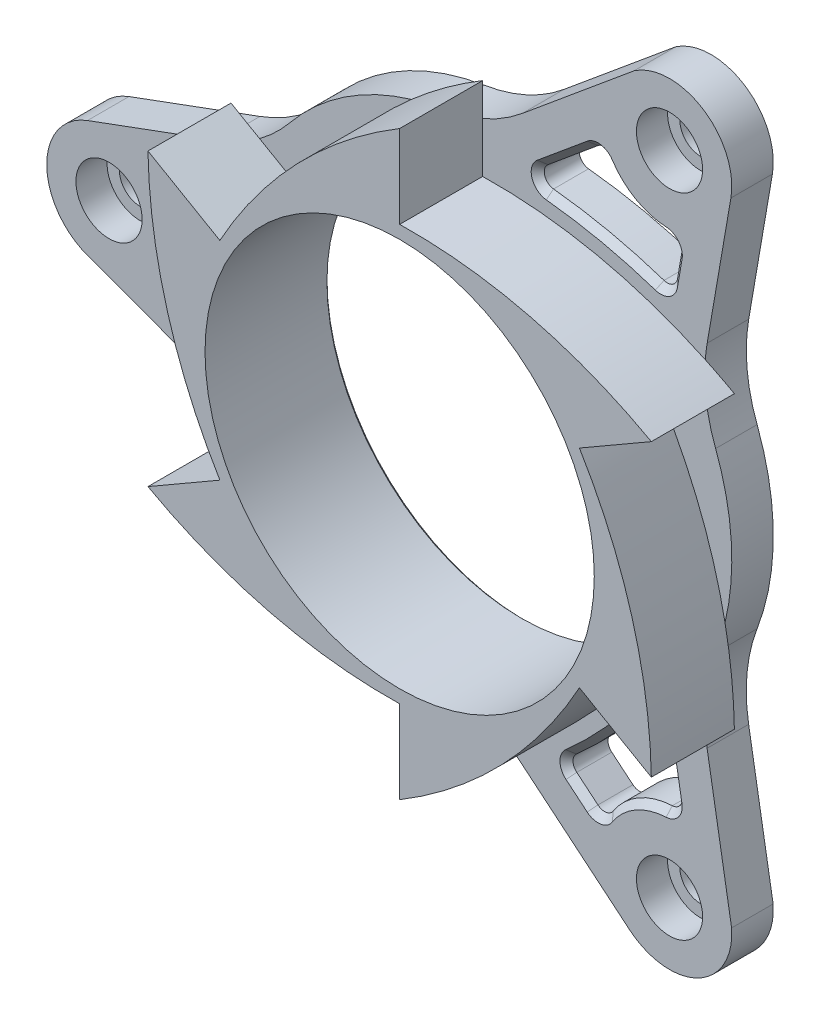
SolidWorks part; units mm, degrees
ref_plane "Front Plane" through (0, 0, 0) normal (0, 0, 1) x (1, 0, 0)
ref_plane "Top Plane" through (0, 0, 0) normal (0, 1, 0) x (1, 0, 0)
ref_plane "Right Plane" through (0, 0, 0) normal (1, 0, 0) x (0, 0, -1)
sketch "Sketch1" plane through (0, 0, 0) normal (0, 0, 1) x (1, 0, 0)
  line L0 (0, 0) -> (0, 31.75) construction
  line L1 (27.4963, 15.875) -> (38.4948, 22.225)
  line L2 (27.4963, -15.875) -> (38.4948, -22.225)
  line L3 (0, -31.75) -> (0, -44.45)
  line L4 (-27.4963, -15.875) -> (-38.4948, -22.225)
  line L5 (-27.4963, 15.875) -> (-38.4948, 22.225)
  line L6 (0, 31.75) -> (0, 44.45)
  line L7 (-20.9623, -0.7492) -> (-20.9623, -0.7492)
  line L8 (-9.8323, -18.5285) -> (-9.8323, -18.5285)
  line L9 (11.13, -17.7793) -> (11.13, -17.7793)
  line L10 (20.9623, 0.7492) -> (20.9623, 0.7492)
  line L11 (9.8323, 18.5285) -> (9.8323, 18.5285)
  line L12 (-11.13, 17.7793) -> (-11.13, 17.7793)
  line L13 (27.4963, 15.875) -> (24.4114, 20.9701) construction
  arc A0 (-11.13, 17.7793) -> (-20.9623, -0.7492) centre (39.2347, -20.8203) ccw
  arc A1 (38.4948, -22.225) -> (27.4963, 15.875) centre (-37.6483, -23.5681) ccw
  arc A2 (38.4948, 22.225) -> (0, 31.75) centre (1.5864, -44.3884) ccw
  arc A3 (0, -44.45) -> (27.4963, -15.875) centre (-39.2347, 20.8203) ccw
  arc A4 (-38.4948, -22.225) -> (0, -31.75) centre (-1.5864, 44.3884) ccw
  arc A5 (-38.4948, 22.225) -> (-27.4963, -15.875) centre (37.6483, 23.5681) ccw
  arc A6 (0, 44.45) -> (-27.4963, 15.875) centre (39.2347, -20.8203) ccw
  arc A7 (-20.9623, -0.7492) -> (-9.8323, -18.5285) centre (37.6483, 23.5681) ccw
  arc A8 (-9.8323, -18.5285) -> (11.13, -17.7793) centre (-1.5864, 44.3884) ccw
  arc A9 (11.13, -17.7793) -> (20.9623, 0.7492) centre (-39.2347, 20.8203) ccw
  arc A10 (20.9623, 0.7492) -> (9.8323, 18.5285) centre (-37.6483, -23.5681) ccw
  arc A11 (9.8323, 18.5285) -> (-11.13, 17.7793) centre (1.5864, -44.3884) ccw
  point P3 (0, 0)
  point P7 (42.5077, 12.9959)
  point P32 (0, 0)
  dimension "D1" = 6
  dimension "D2" = 12.7
  dimension "D3" = 60
extrude "Boss-Extrude1" add sketch "Sketch1" along normal blind 6.35 and the other way blind 6.35
sketch "Sketch3" plane through (0, 0, 6.35) normal (0, 0, 1) x (1, 0, 0)
  arc A0 (-11.13, 17.7793) -> (-20.9623, -0.7492) centre (39.2347, -20.8203) ccw construction
  arc A1 (9.8323, 18.5285) -> (-11.13, 17.7793) centre (1.5864, -44.3884) ccw construction
  arc A2 (20.9623, 0.7492) -> (9.8323, 18.5285) centre (-37.6483, -23.5681) ccw construction
  arc A3 (11.13, -17.7793) -> (20.9623, 0.7492) centre (-39.2347, 20.8203) ccw construction
  arc A4 (-9.8323, -18.5285) -> (11.13, -17.7793) centre (-1.5864, 44.3884) ccw construction
  arc A5 (-20.9623, -0.7492) -> (-9.8323, -18.5285) centre (37.6483, 23.5681) ccw construction
  arc A6 (-11.13, 17.7793) -> (-20.9623, -0.7492) centre (39.2347, -20.8203) ccw
  arc A7 (9.8323, 18.5285) -> (-11.13, 17.7793) centre (1.5864, -44.3884) ccw
  arc A8 (20.9623, 0.7492) -> (9.8323, 18.5285) centre (-37.6483, -23.5681) ccw
  arc A9 (11.13, -17.7793) -> (20.9623, 0.7492) centre (-39.2347, 20.8203) ccw
  arc A10 (-9.8323, -18.5285) -> (11.13, -17.7793) centre (-1.5864, 44.3884) ccw
  arc A11 (-20.9623, -0.7492) -> (-9.8323, -18.5285) centre (37.6483, 23.5681) ccw
extrude "Boss-Extrude2" add sketch "Sketch3" against normal blind 12.7
sketch "Sketch5" plane through (0, 0, -6.35) normal (0, 0, -1) x (-1, 0, 0)
  line L0 (0, 0) -> (57.15, 0) construction
  line L1 (0, 0) -> (0, 28.575) construction
  line L2 (32.9956, 19.05) -> (60.4429, 8.9377)
  line L3 (27.4963, 15.875) -> (38.4948, 22.225) construction
  line L4 (32.9956, -19.05) -> (61.2521, -8.5964)
  line L5 (0, -38.1) -> (-22.4812, -56.8139)
  line L6 (-32.9956, -19.05) -> (-38.0708, -48.7477)
  line L7 (-32.9956, 19.05) -> (-37.9617, 47.8762)
  line L8 (0, 38.1) -> (-23.1814, 57.3441)
  arc A0 (32.9956, 19.05) -> (0, 38.1) centre (0, 0) ccw
  circle A1 centre (0, 0) radius 28.575
  circle A2 centre (0, 0) radius 57.15 construction
  circle A3 centre (57.15, 0) radius 3.175
  arc A4 (61.2521, -8.5964) -> (60.4429, 8.9377) centre (57.15, 0) ccw
  circle A5 centre (-28.575, -49.4934) radius 3.175
  circle A6 centre (57.15, 0) radius 9.525 construction
  arc A7 (-38.0708, -48.7477) -> (-22.4812, -56.8139) centre (-28.575, -49.4934) ccw
  circle A8 centre (-28.575, 49.4934) radius 3.175
  arc A9 (-23.1814, 57.3441) -> (-37.9617, 47.8762) centre (-28.575, 49.4934) ccw
  arc A10 (-32.9956, 19.05) -> (-32.9956, -19.05) centre (0, 0) ccw
  arc A11 (0, -38.1) -> (32.9956, -19.05) centre (0, 0) ccw
  point P1 (60.325, 0)
  point P32 (0, 0)
  dimension "D1" = 90
  dimension "D2" = 6.35
  dimension "D5" = 114.3
  dimension "D3" = 6.35
  dimension "D4" = 3
extrude "Boss-Extrude3" add sketch "Sketch5" along normal blind 6.35
sketch "Sketch4" plane through (0, 0, 6.35) normal (0, 0, 1) x (1, 0, 0)
  circle A0 centre (0, 0) radius 29.7688
  dimension "D1" = 59.5375
extrude "Cut-Extrude1" cut sketch "Sketch4" against normal through all
fillet "Fillet1" radius 25.4 6 edges at (0, -38.1, -9.525) (-32.9956, -19.05, -9.525) (-32.9956, 19.05, -9.525) (0, 38.1, -9.525) (32.9956, 19.05, -9.525) (32.9956, -19.05, -9.525)
chamfer "Chamfer1" distance 0.4 angle 45 1 edges at (29.7688, 0, -12.7)
sketch "Sketch6" plane through (0, 0, -6.35) normal (0, 0, 1) x (1, 0, 0)
  circle A0 centre (-57.15, 0) radius 5.0625
  circle A1 centre (28.575, 49.4934) radius 5.0625
  circle A2 centre (28.575, -49.4934) radius 5.0625
  point P9 (0, 0)
  dimension "D1" = 10.125
  dimension "D2" = 3
extrude "Cut-Extrude2" cut sketch "Sketch6" against normal blind 4.7625
chamfer "Chamfer2" distance 0.4 angle 45 3 edges at (-60.325, 0, -12.7) (25.4, -49.4934, -12.7) (25.4, 49.4934, -12.7)
sketch "Sketch7" plane through (0, 0, -6.35) normal (0, 0, 1) x (1, 0, 0)
  line L0 (-47.9616, 6.7689) -> (-40.432, 9.543)
  line L1 (-60.4429, 8.9377) -> (-40.4143, 16.3168) construction
  line L2 (-47.9464, -6.7483) -> (-33.1491, -12.2226)
  line L3 (-40.3955, -16.3124) -> (-61.2521, -8.5964) construction
  line L4 (18.129, 44.897) -> (5.9895, 34.8192)
  line L5 (29.8428, 38.1515) -> (28.4805, 30.2437)
  line L6 (29.8174, -38.1487) -> (27.1596, -22.5967)
  line L7 (18.1188, -44.9204) -> (11.9516, -39.7867)
  arc A2 (-41.6693, 22.169) -> (-30.2123, -17.5194) centre (37.6483, 23.5681) ccw
  arc A3 (-40.432, 9.543) -> (-33.1491, -12.2226) centre (37.6483, 23.5681) ccw
  arc A5 (18.129, 44.897) -> (29.8428, 38.1515) centre (28.575, 49.4934) ccw
  circle A6 centre (-57.15, 0) radius 11.4125
  arc A7 (-47.9464, -6.7483) -> (-47.9616, 6.7689) centre (-57.15, 0) ccw
  arc A8 (28.4805, 30.2437) -> (5.9895, 34.8192) centre (1.5864, -44.3884) ccw
  arc A9 (29.8174, -38.1487) -> (18.1188, -44.9204) centre (28.575, -49.4934) ccw
  arc A10 (11.9516, -39.7867) -> (27.1596, -22.5967) centre (-39.2347, 20.8203) ccw
  point P27 (0, 0)
  dimension "D3" = 6.35
  dimension "D4" = 6.35
  dimension "D1" = 3.175
  dimension "D2" = 6.35
  dimension "D5" = 3
extrude "Cut-Extrude3" cut sketch "Sketch7" against normal through all
fillet "Fillet2" radius 1.5875 12 edges at (29.8174, -38.1487, -9.525) (18.1188, -44.9204, -9.525) (27.1596, -22.5967, -9.525) (11.9516, -39.7867, -9.525) (5.9895, 34.8192, -9.525) (28.4805, 30.2437, -9.525) (29.8428, 38.1515, -9.525) (18.129, 44.897, -9.525) (-40.432, 9.543, -9.525) (-47.9616, 6.7689, -9.525) (-47.9464, -6.7483, -9.525) (-33.1491, -12.2226, -9.525)
chamfer "Chamfer3" distance 1 angle 45 24 edges at (17.8838, -44.0277, -6.35) (22.8603, -39.6147, -6.35) (29.1653, -37.5026, -6.35) (28.6542, -31.3423, -6.35) (26.6128, -25.1639, -6.35) (19.5096, -32.4934, -6.35) (12.8178, -39.7877, -6.35) (15.0083, -42.3312, -6.35) (-47.0608, -6.5066, -6.35) (-41.4703, -9.1441, -6.35) (-35.099, -10.4654, -6.35) (-37.8949, -0.6491, -6.35) (-40.8661, 8.7933, -6.35) (-44.164, 8.168, -6.35) (-47.071, 6.526, -6.35) (-45.7375, 0.0097, -6.35) (29.1872, 37.5017, -6.35) (29.1557, 34.1632, -6.35) (28.0483, 30.9944, -6.35) (18.3853, 33.1425, -6.35) (8.4862, 35.6294, -6.35) (22.8772, 39.605, -6.35) (17.8955, 44.0092, -6.35) (12.8161, 40.4864, -6.35)
